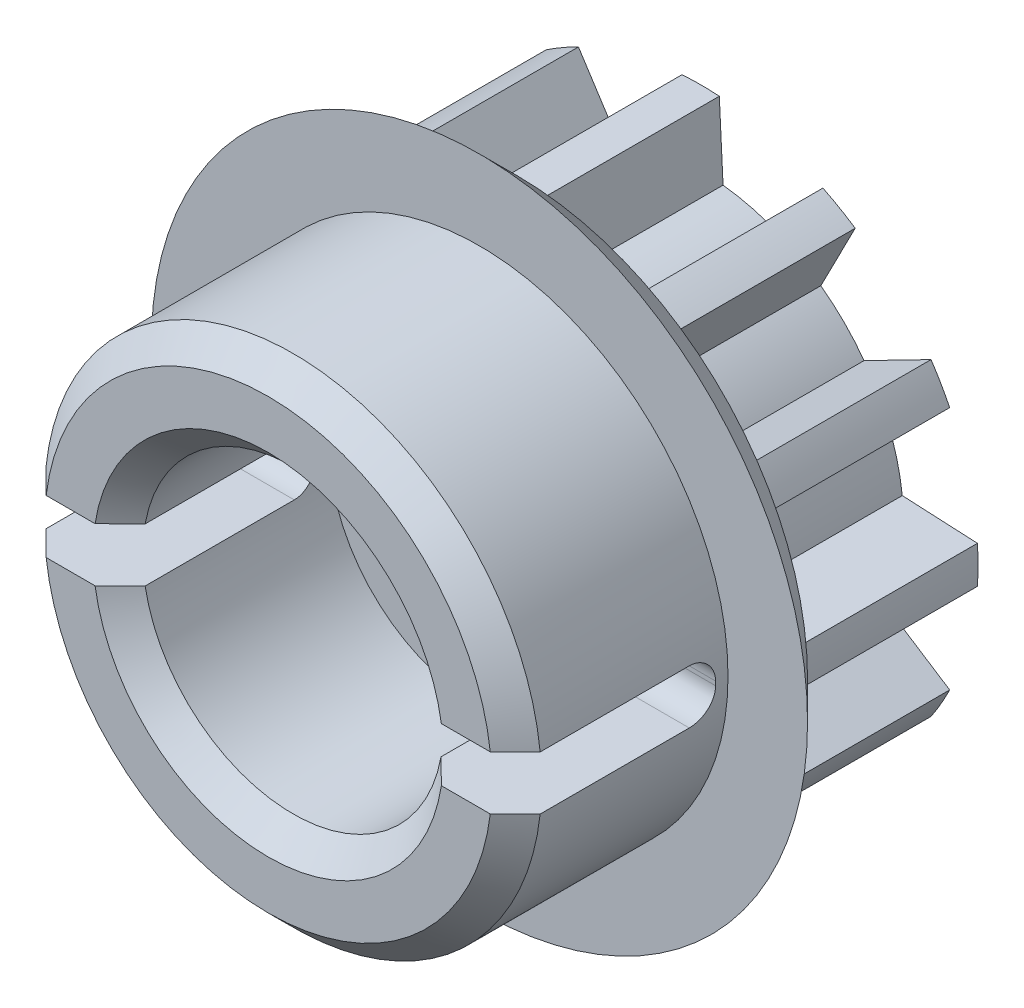
SolidWorks part; units mm, degrees
material "ABS"
ref_plane "Alzado" through (0, 0, 0) normal (0, 0, 1) x (1, 0, 0)
ref_plane "Planta" through (0, 0, 0) normal (0, 1, 0) x (1, 0, 0)
ref_plane "Vista lateral" through (0, 0, 0) normal (1, 0, 0) x (0, 0, -1)
sketch "Croquis1" plane through (0, 0, 0) normal (0, 0, 1) x (1, 0, 0)
  line L0 (0, 0) -> (0, 4.6049) construction
  line L1 (0.375, 5.5679) -> (0.45, 4.0556)
  line L2 (-0.375, 5.5679) -> (-0.45, 4.0556)
  line L3 (2.4592, 5.0094) -> (1.6381, 3.7373)
  line L4 (3.1087, 4.6344) -> (2.4175, 3.2873)
  line L5 (4.6344, 3.1087) -> (3.2873, 2.4175)
  line L6 (5.0094, 2.4592) -> (3.7373, 1.6381)
  line L7 (5.5679, 0.375) -> (4.0556, 0.45)
  line L8 (5.5679, -0.375) -> (4.0556, -0.45)
  line L9 (5.0094, -2.4592) -> (3.7373, -1.6381)
  line L10 (4.6344, -3.1087) -> (3.2873, -2.4175)
  line L11 (3.1087, -4.6344) -> (2.4175, -3.2873)
  line L12 (2.4592, -5.0094) -> (1.6381, -3.7373)
  line L13 (0.375, -5.5679) -> (0.45, -4.0556)
  line L14 (-0.375, -5.5679) -> (-0.45, -4.0556)
  line L15 (-2.4592, -5.0094) -> (-1.6381, -3.7373)
  line L16 (-3.1087, -4.6344) -> (-2.4175, -3.2873)
  line L17 (-4.6344, -3.1087) -> (-3.2873, -2.4175)
  line L18 (-5.0094, -2.4592) -> (-3.7373, -1.6381)
  line L19 (-5.5679, -0.375) -> (-4.0556, -0.45)
  line L20 (-5.5679, 0.375) -> (-4.0556, 0.45)
  line L21 (-5.0094, 2.4592) -> (-3.7373, 1.6381)
  line L22 (-4.6344, 3.1087) -> (-3.2873, 2.4175)
  line L23 (-3.1087, 4.6344) -> (-2.4175, 3.2873)
  line L24 (-2.4592, 5.0094) -> (-1.6381, 3.7373)
  circle A0 centre (0, 0) radius 1.85
  arc A1 (1.6381, 3.7373) -> (0.45, 4.0556) centre (0, 0) ccw
  arc A2 (3.1087, 4.6344) -> (2.4592, 5.0094) centre (0, 0) ccw
  arc A3 (5.0094, 2.4592) -> (4.6344, 3.1087) centre (0, 0) ccw
  arc A4 (5.5679, -0.375) -> (5.5679, 0.375) centre (0, 0) ccw
  arc A5 (4.6344, -3.1087) -> (5.0094, -2.4592) centre (0, 0) ccw
  arc A6 (2.4592, -5.0094) -> (3.1087, -4.6344) centre (0, 0) ccw
  arc A7 (-0.375, -5.5679) -> (0.375, -5.5679) centre (0, 0) ccw
  arc A8 (-3.1087, -4.6344) -> (-2.4592, -5.0094) centre (0, 0) ccw
  arc A9 (-5.0094, -2.4592) -> (-4.6344, -3.1087) centre (0, 0) ccw
  arc A10 (-5.5679, 0.375) -> (-5.5679, -0.375) centre (0, 0) ccw
  arc A11 (-4.6344, 3.1087) -> (-5.0094, 2.4592) centre (0, 0) ccw
  arc A12 (-2.4592, 5.0094) -> (-3.1087, 4.6344) centre (0, 0) ccw
  arc A13 (0.375, 5.5679) -> (-0.375, 5.5679) centre (0, 0) ccw
  arc A14 (3.2873, 2.4175) -> (2.4175, 3.2873) centre (0, 0) ccw
  arc A15 (4.0556, 0.45) -> (3.7373, 1.6381) centre (0, 0) ccw
  arc A16 (3.7373, -1.6381) -> (4.0556, -0.45) centre (0, 0) ccw
  arc A17 (2.4175, -3.2873) -> (3.2873, -2.4175) centre (0, 0) ccw
  arc A18 (0.45, -4.0556) -> (1.6381, -3.7373) centre (0, 0) ccw
  arc A19 (-1.6381, -3.7373) -> (-0.45, -4.0556) centre (0, 0) ccw
  arc A20 (-3.2873, -2.4175) -> (-2.4175, -3.2873) centre (0, 0) ccw
  arc A21 (-4.0556, -0.45) -> (-3.7373, -1.6381) centre (0, 0) ccw
  arc A22 (-3.7373, 1.6381) -> (-4.0556, 0.45) centre (0, 0) ccw
  arc A23 (-2.4175, 3.2873) -> (-3.2873, 2.4175) centre (0, 0) ccw
  arc A24 (-0.45, 4.0556) -> (-1.6381, 3.7373) centre (0, 0) ccw
  dimension "D1" = 0.9
  dimension "D2" = 3.7
  dimension "D4" = 1.5
  dimension "D3" = 0.75
  dimension "D6" = 1.23
  dimension "D5" = 12
extrude "Saliente-Extruir1" add sketch "Croquis1" along normal blind 3.7
sketch "Croquis2" plane through (0, 0, 3.7) normal (0, 0, 1) x (1, 0, 0)
  circle A0 centre (0, 0) radius 3.025
  circle A1 centre (0, 0) radius 5
  dimension "D1" = 10
  dimension "D2" = 6.05
extrude "Saliente-Extruir2" add sketch "Croquis2" along normal blind 5
chamfer "Chaflán1" distance 0.5 angle 45 1 edges at (5, 0, 8.7)
sketch "Croquis8" plane through (0, 0, 0) normal (0, 0, -1) x (-1, 0, 0)
  line L1 (-1.4818, -2.3418) -> (1.2872, -2.4542)
  line L2 (1.2872, -2.4542) -> (2.769, -0.1124)
  line L3 (2.769, -0.1124) -> (1.4818, 2.3418)
  line L4 (1.4818, 2.3418) -> (-1.2872, 2.4542)
  line L5 (-1.2872, 2.4542) -> (-2.769, 0.1124)
  line L6 (-2.769, 0.1124) -> (-1.4818, -2.3418)
  circle A0 centre (0, 0) radius 2.4 construction
  dimension "D1" = 4.8
extrude "Cortar-Extruir1" cut sketch "Croquis8" against normal blind 2.5
chamfer "Chaflán2" distance 0.5 angle 45 1 edges at (3.025, 0, 8.7)
sketch "Croquis4" plane through (0, 0, 3.7) normal (0, 0, 1) x (1, 0, 0)
  circle A0 centre (0, 0) radius 1.85
  circle A1 centre (0, 0) radius 4.8926
  circle A2 centre (0, 0) radius 1.85 construction
extrude "Saliente-Extruir4" add sketch "Croquis4" along normal blind 0.1
chamfer "Chaflán3" distance 0.5 angle 45 12 edges at (3.9415, 1.0561, 3.7) (2.8853, 2.8853, 3.7) (1.0561, 3.9415, 3.7) (-1.0561, 3.9415, 3.7) (-2.8853, 2.8853, 3.7) (-3.9415, -1.0561, 3.7) (-3.9415, 1.0561, 3.7) (-2.8853, -2.8853, 3.7) (-1.0561, -3.9415, 3.7) (1.0561, -3.9415, 3.7) (2.8853, -2.8853, 3.7) (3.9415, -1.0561, 3.7)
sketch "Croquis6" plane through (0, 0, 3.7) normal (0, 0, 1) x (1, 0, 0)
  circle A0 centre (0, 0) radius 6.75
  circle A2 centre (0, 0) radius 1.85
  circle A4 centre (0, 0) radius 1.85 construction
  dimension "D1" = 13.5
extrude "Saliente-Extruir5" add sketch "Croquis6" along normal blind 0.75
chamfer "Chaflán5" distance 0.9 angle 45 1 edges at (6.75, 0, 3.7)
chamfer "Chaflán7" distance 1 angle 45 1 edges at (-1.85, 0, 2.5)
sketch "Croquis9" plane through (0, 0, 8.7) normal (0, 0, 1) x (1, 0, 0)
  line L0 (5.7484, 0) -> (-6.3843, 0) construction
  line L1 (5.7026, -0.5408) -> (5.7026, 0.5408)
  line L2 (5.7026, 0.5408) -> (-5.9897, 0.5408)
  line L3 (-5.9897, 0.5408) -> (-5.9897, -0.5408)
  line L4 (-5.9897, -0.5408) -> (5.7026, -0.5408)
extrude "Cortar-Extruir2" cut sketch "Croquis9" along direction (0, 0, 1) on the side against the normal blind 4
fillet "Redondeo1" radius 0.5 4 edges at (3.9735, -0.5408, 4.7) (3.9735, 0.5408, 4.7) (-3.9735, -0.5408, 4.7) (-3.9735, 0.5408, 4.7)
chamfer "Chamfer1" distance 0.5 angle 45 6 edges at (-0.0973, 2.398, 0) (-2.1254, 1.1147, 0) (-2.0281, -1.2833, 0) (0.0973, -2.398, 0) (2.0281, 1.2833, 0) (2.1254, -1.1147, 0)
